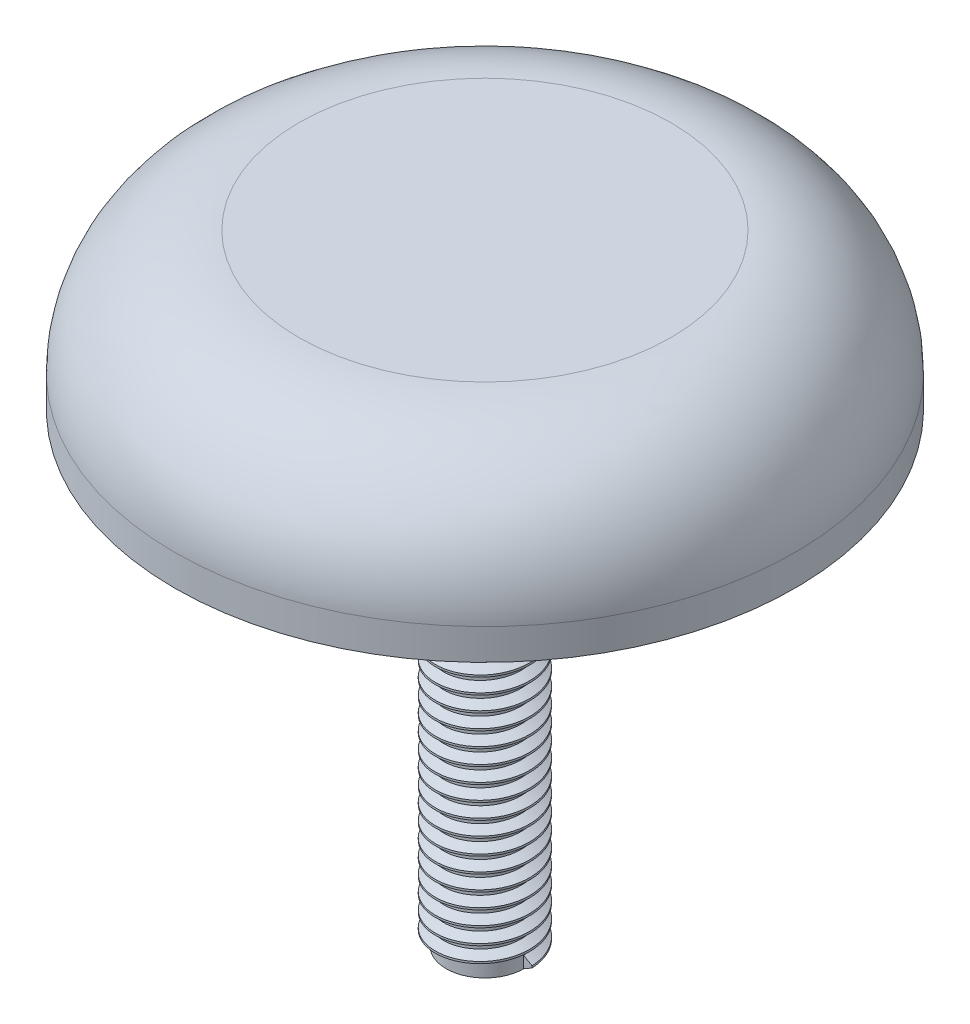
SolidWorks part; units mm, degrees
ref_plane "Спереди" through (0, 0, 0) normal (0, 0, 1) x (1, 0, 0)
ref_plane "Сверху" through (0, 0, 0) normal (0, 1, 0) x (1, 0, 0)
ref_plane "Справа" through (0, 0, 0) normal (1, 0, 0) x (0, 0, -1)
sketch "Эскиз1" plane through (0, 0, 0) normal (0, 1, 0) x (1, 0, 0)
  circle A0 centre (0, 0) radius 2.5
  dimension "D1" = 5
extrude "Бобышка-Вытянуть1" add sketch "Эскиз1" along normal blind 30
sketch "Эскиз2" plane through (0, 30, 0) normal (0, 1, 0) x (1, 0, 0)
  circle A0 centre (0, 0) radius 20
  dimension "D1" = 40
extrude "Бобышка-Вытянуть2" add sketch "Эскиз2" along normal blind 10
fillet "Скругление1" radius 8 1 edges at (0, 40, 20)
thread "Резьба1" pitch 1 method extrude profile "Профиль резьбы2" start angle 0, offset 0, length 0, pitch 1, diameter 5
ref_plane "Плоскость5" through (2.5, 0, 0) normal (0, 0, 1) x (1, 0, 0)
sketch "Профиль резьбы2" plane through (2.5, 0, 0) normal (0, 0, 1) x (1, 0, 0)
  line L0 (0, 0) -> (0, 1) construction
  line L1 (0, 0) -> (0.5413, 0.3125)
  line L2 (0.5413, 0.3125) -> (0.5413, 0.4375)
  line L3 (0.5413, 0.4375) -> (0, 0.75)
  line L4 (0.5413, 0.375) -> (0, 0.375) construction
  line L11 (0, 0) -> (0, 0.75)
  point P2 (0, 0)
  dimension "Pitch" = 1
  dimension "Profile_Angle" = 60
  dimension "Profile_Land" = 0.125
  dimension "Profile_Height" = 0.5413
